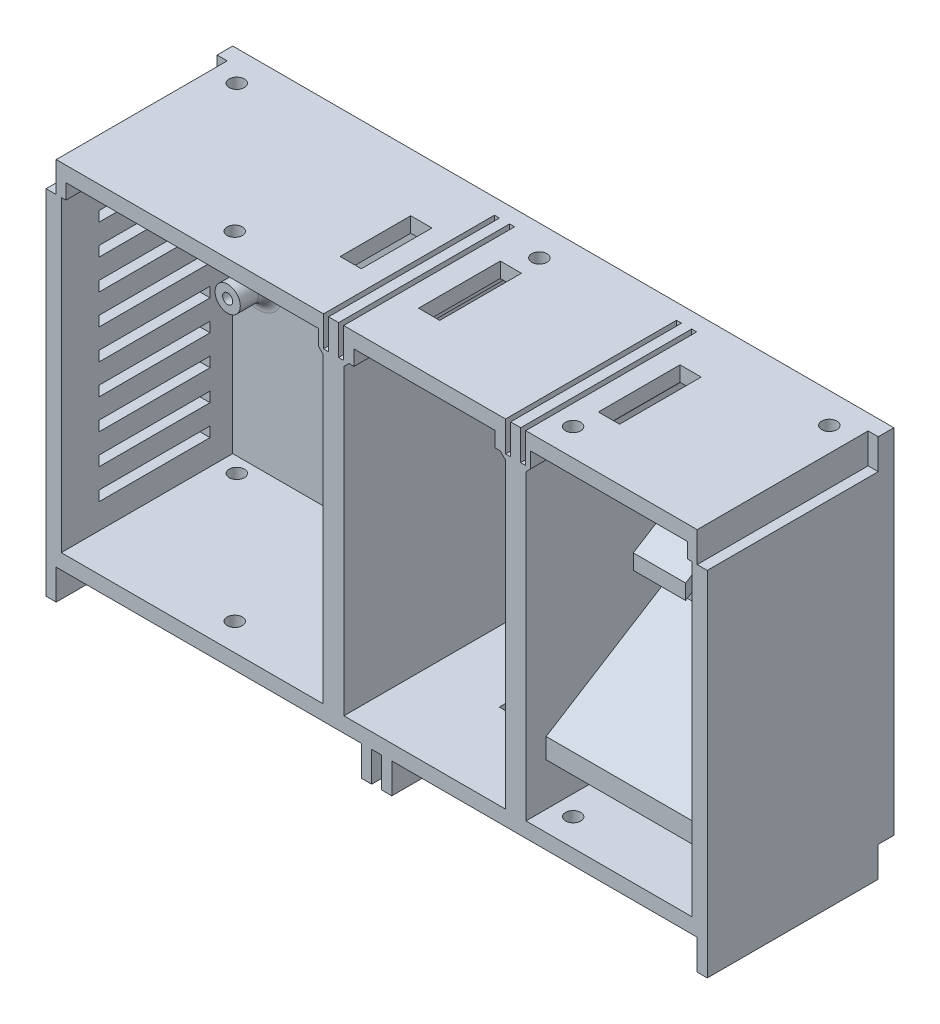
SolidWorks part; units mm, degrees
material "ABS"
ref_plane "Alzado" through (0, 0, 0) normal (0, 0, 1) x (1, 0, 0)
ref_plane "Planta" through (0, 0, 0) normal (0, 1, 0) x (1, 0, 0)
ref_plane "Vista lateral" through (0, 0, 0) normal (1, 0, 0) x (0, 0, -1)
sketch "Croquis1" plane through (0, 0, 0) normal (0, 0, 1) x (1, 0, 0)
  line L0 (0, 0) -> (2, 0)
  line L1 (2, 0) -> (2, 6)
  line L2 (55, 0) -> (55, 6)
  line L3 (55, 6) -> (2, 6)
  line L4 (56, 0) -> (56, 6)
  line L5 (56, 6) -> (58, 6)
  line L6 (58, 6) -> (58, 0)
  line L7 (58, 0) -> (59, 0)
  line L8 (59, 0) -> (59, 6)
  line L9 (91.1, 0) -> (91.1, 6)
  line L10 (59, 6) -> (91.1, 6)
  line L11 (92.1, 0) -> (92.1, 6)
  line L12 (92.1, 6) -> (94.1, 6)
  line L13 (94.1, 6) -> (94.1, 0)
  line L14 (95.1, 0) -> (95.1, 6)
  line L15 (129.1, 0) -> (129.1, 6)
  line L16 (129.1, 6) -> (95.1, 6)
  line L17 (0, 0) -> (0, -64)
  line L18 (0, -64) -> (131.1, -64)
  line L19 (131.1, -64) -> (131.1, 0)
  line L20 (55, 0) -> (56, 0)
  line L21 (58, 0) -> (59, 0)
  line L22 (129.1, 0) -> (131.1, 0)
  line L23 (94.1, 0) -> (95.1, 0)
  line L24 (91.1, 0) -> (92.1, 0)
  line L25 (2, 0) -> (129.1, 0)
  point P3 (2, 0)
  point P4 (129.1, 0)
  point P5 (55, 0)
  point P10 (56, 0)
  point P11 (58, 0)
  point P12 (59, 0)
  point P15 (91.1, 0)
  point P22 (92.1, 0)
  point P23 (94.1, 0)
  point P24 (95.1, 0)
  dimension "D1" = 131.1
  dimension "D2" = 2
  dimension "D3" = 2
  dimension "D4" = 55
  dimension "D5" = 6
  dimension "D6" = 1
  dimension "D7" = 2
  dimension "D8" = 1
  dimension "D9" = 32.1
  dimension "D10" = 1
  dimension "D11" = 2
  dimension "D12" = 1
  dimension "D13" = 64
extrude "Saliente-Extruir1" add sketch "Croquis1" along normal blind 34 contours L8 L25 L9 L10 | L1 L25 L2 L3 | L14 L25 L15 L16 | L11 L25 L13 L12 | L4 L25 L6 L5 region at (28.5, 3, 0) region at (57, 3, 0) region at (112.1, 3, 0) region at (75.05, 3, 0) region at (93.1, 3, 0)
sketch "Croquis2" plane through (0, 0, 0) normal (0, 0, 1) x (1, 0, 0)
  line L1 (2, -64) -> (129.1, -64)
  line L3 (129.1, 0) -> (2, 0)
  line L5 (129.1, 0) -> (131.1, 0)
  line L7 (129.1, -64) -> (131.1, -64)
  line L8 (131.1, 0) -> (131.1, -64)
  line L9 (2, -64) -> (0, -64)
  line L11 (2, 0) -> (0, 0)
  line L12 (0, -64) -> (0, 0)
  dimension "D1" = 64
  dimension "D2" = 2
  dimension "D3" = 2
extrude "Saliente-Extruir2" add sketch "Croquis2" along normal blind 3
sketch "Croquis3" plane through (0, 0, 3) normal (0, 0, 1) x (1, 0, 0)
  line L0 (0, -64) -> (131.1, -64) construction
  line L1 (131.1, 0) -> (128.1, 0)
  line L2 (131.1, 0) -> (131.1, -64)
  line L3 (131.1, -64) -> (128.1, -64)
  line L4 (128.1, 0) -> (128.1, -61)
  line L6 (0, 0) -> (3, 0)
  line L7 (0, 0) -> (0, -64)
  line L8 (0, -64) -> (3, -64)
  line L9 (3, 0) -> (3, -61)
  line L10 (3, -64) -> (128.1, -64)
  line L12 (3, -61) -> (128.1, -61)
  dimension "D1" = 3
  dimension "D2" = 3
  dimension "D3" = 3
extrude "Saliente-Extruir3" add sketch "Croquis3" along normal up to vertex (31 mm away) up to point (129.1, 0, 34)
sketch "Croquis4" plane through (0, 0, 0) normal (0, 0, -1) x (-1, 0, 0)
  line L24 (-59, 0) -> (-59, 6)
  line L25 (-59, 6) -> (-91.1, 6)
  line L26 (-91.1, 6) -> (-91.1, 0)
  line L27 (-91.1, 0) -> (-92.1, 0)
  line L28 (-92.1, 0) -> (-92.1, 6)
  line L29 (-92.1, 6) -> (-94.1, 6)
  line L30 (-94.1, 6) -> (-94.1, 0)
  line L31 (-94.1, 0) -> (-95.1, 0)
  line L32 (-95.1, 0) -> (-95.1, 6)
  line L33 (-95.1, 6) -> (-129.1, 6)
  line L34 (-129.1, 6) -> (-129.1, 0)
  line L35 (-129.1, 0) -> (-131.1, 0)
  line L36 (-131.1, 0) -> (-131.1, -64)
  line L37 (-131.1, -64) -> (0, -64)
  line L38 (0, -64) -> (0, 0)
  line L39 (0, 0) -> (-2, 0)
  line L40 (-2, 0) -> (-2, 6)
  line L41 (-2, 6) -> (-55, 6)
  line L42 (-55, 6) -> (-55, 0)
  line L43 (-55, 0) -> (-56, 0)
  line L44 (-56, 0) -> (-56, 6)
  line L45 (-56, 6) -> (-58, 6)
  line L46 (-58, 6) -> (-58, 0)
  line L47 (-58, 0) -> (-59, 0)
  line L48 (-59, 0) -> (-59, 6)
  line L49 (-59, 6) -> (-91.1, 6)
  line L50 (-91.1, 6) -> (-91.1, 0)
  line L51 (-91.1, 0) -> (-92.1, 0)
  line L52 (-92.1, 0) -> (-92.1, 6)
  line L53 (-92.1, 6) -> (-94.1, 6)
  line L54 (-94.1, 6) -> (-94.1, 0)
  line L55 (-94.1, 0) -> (-95.1, 0)
  line L56 (-95.1, 0) -> (-95.1, 6)
  line L57 (-95.1, 6) -> (-129.1, 6)
  line L58 (-129.1, 6) -> (-129.1, 0)
  line L59 (-129.1, 0) -> (-131.1, 0)
  line L60 (-131.1, 0) -> (-131.1, -64)
  line L61 (-131.1, -64) -> (0, -64)
  line L62 (0, -64) -> (0, 0)
  line L63 (0, 0) -> (-2, 0)
  line L64 (-2, 0) -> (-2, 6)
  line L65 (-2, 6) -> (-55, 6)
  line L66 (-55, 6) -> (-55, 0)
  line L67 (-55, 0) -> (-56, 0)
  line L68 (-56, 0) -> (-56, 6)
  line L69 (-56, 6) -> (-58, 6)
  line L70 (-58, 6) -> (-58, 0)
  line L71 (-58, 0) -> (-59, 0)
  dimension "D1" = 0
extrude "Saliente-Extruir4" add sketch "Croquis4" along normal blind 3
sketch "Croquis5" plane through (0, 0, 3) normal (0, 0, 1) x (1, 0, 0)
  line L1 (128.1, -61) -> (3, -61) construction
  line L23 (54.95, 0.05) -> (59.05, 0.05)
  line L24 (55, 0) -> (55, 6) construction
  line L25 (59, 0) -> (59, 6) construction
  line L26 (58, 0) -> (56, 0) construction
  line L27 (54.95, 0.05) -> (54.95, -61)
  line L28 (59.05, 0.05) -> (59.05, -61)
  line L29 (91.05, 0.05) -> (95.15, 0.05)
  line L30 (91.1, 0) -> (91.1, 6) construction
  line L31 (95.1, 0) -> (95.1, 6) construction
  line L32 (95.1, 0) -> (94.1, 0) construction
  line L33 (91.05, 0.05) -> (91.05, -61)
  line L34 (128.1, -61) -> (3, -61) construction
  line L35 (91.05, -61) -> (95.15, -61)
  line L36 (95.15, -61) -> (95.15, 0.05)
  line M6 (128.1, 0) -> (95.1, 0)
  line M7 (95.1, 0) -> (94.1, 0)
  line M8 (94.1, 0) -> (92.1, 0)
  line M9 (92.1, 0) -> (91.1, 0)
  line M10 (91.1, 0) -> (59, 0)
  line M11 (59, 0) -> (58, 0)
  line M12 (58, 0) -> (56, 0)
  line M13 (56, 0) -> (55, 0)
  line M14 (55, 0) -> (3, 0)
  line M16 (3, -61) -> (128.1, -61)
  dimension "D1" = 0.05
  dimension "D2" = 0.05
  dimension "D3" = 0.05
  dimension "D4" = 0.05
  dimension "D5" = 0.05
  dimension "D6" = 0.05
extrude "Saliente-Extruir10" add sketch "Croquis5" along normal up to vertex (31 mm away) contours L28 L27 M10 M11 M12 M13 M14 M16 | L36 L33 M16 M6 M7 M8 M9 M10 region at (57, -30.5, 3) region at (93.1, -30.5, 3) up to point (59, 0, 34)
sketch "Croquis6" plane through (0, 0, 0) normal (0, -1, 0) x (1, 0, 0)
  line L0 (0, 34) -> (0, -3) construction
  line L1 (0, 15.5) -> (131.1, 15.5) construction
  line L2 (131.1, 34) -> (131.1, -3) construction
  line L3 (51, 8.5) -> (51, 22.5)
  line L4 (51, 22.5) -> (46.8, 22.5)
  line L5 (46.8, 22.5) -> (46.8, 8.5)
  line L6 (46.8, 8.5) -> (51, 8.5)
  line L7 (99.1, 7.4) -> (99.1, 23.6)
  line L8 (99.1, 23.6) -> (103.3, 23.6)
  line L9 (103.3, 23.6) -> (103.3, 7.4)
  line L10 (103.3, 7.4) -> (99.1, 7.4)
  line L11 (63.45, 7.4) -> (63.45, 23.6)
  line L12 (63.45, 23.6) -> (67.65, 23.6)
  line L13 (67.65, 23.6) -> (67.65, 7.4)
  line L14 (67.65, 7.4) -> (63.45, 7.4)
  point P6 (99.1, 15.5)
  point P9 (51, 15.5)
  point P15 (99.1, 15.5)
  point P17 (63.45, 15.5)
  point P21 (63.45, 15.5)
  dimension "D1" = 51
  dimension "D2" = 4.2
  dimension "D3" = 14
  dimension "D4" = 32
  dimension "D5" = 16.2
  dimension "D6" = 4.2
  dimension "D7" = 12.45
extrude "Cortar-Extruir1" cut sketch "Croquis6" against normal up to next
sketch "Croquis7" plane through (0, 0, 34) normal (0, 0, 1) x (1, 0, 0)
  line L0 (3, 0) -> (54.95, 0) construction
  line L1 (28.975, 0) -> (28.975, 3)
  line L2 (3.925, 3) -> (54.025, 3)
  line L3 (54.025, 3) -> (54.025, 0)
  line L4 (3.925, 0) -> (54.025, 0)
  line L5 (3.925, 3) -> (3.925, 0)
  line L6 (75.05, 0) -> (75.05, 3)
  line L7 (59.05, 0) -> (91.05, 0) construction
  line L8 (75.05, 3) -> (89.05, 3)
  line L9 (89.05, 3) -> (89.05, 0)
  line L10 (89.05, 0) -> (75.05, 0)
  line L11 (75.05, 3) -> (61.05, 3)
  line L12 (61.05, 3) -> (61.05, 0)
  line L13 (61.05, 0) -> (75.05, 0)
  line L14 (61.05, 3) -> (75.05, 3)
  line L15 (111.625, 0) -> (111.625, 3)
  line L16 (95.15, 0) -> (128.1, 0) construction
  line L17 (111.625, 3) -> (127.225, 3)
  line L18 (127.225, 3) -> (127.225, 0)
  line L19 (127.225, 0) -> (111.625, 0)
  line L20 (111.625, 0) -> (96.025, 0)
  line L21 (96.025, 0) -> (96.025, 3)
  line L22 (96.025, 3) -> (111.625, 3)
  line M5 (59.05, 0) -> (91.05, 0)
  line M10 (95.15, 0) -> (128.1, 0)
  line M37 (3, 0) -> (54.95, 0)
  dimension "D1" = 25.05
  dimension "D2" = 3
  dimension "D3" = 14
  dimension "D4" = 15.6
extrude "Cortar-Extruir2" cut sketch "Croquis7" against normal up to vertex (31 mm away) contours L3 L2 L1 M37 | L2 L5 L1 M37 | L11 L12 L6 M5 | L9 L8 L6 M5 | L22 L21 L15 M10 | L18 L17 L15 M10 region at (16.45, 1.5, 34) region at (41.5, 1.5, 34) region at (68.05, 1.5, 34) region at (82.05, 1.5, 34) region at (103.825, 1.5, 34) region at (119.425, 1.5, 34) up to point (54.95, 0, 3)
sketch "Croquis22" plane through (0, 0, 3) normal (0, 0, 1) x (1, 0, 0)
  line L0 (95.15, 0) -> (95.15, -61) construction
  line L1 (95.15, -61) -> (128.1, -61) construction
  line L2 (128.1, -61) -> (128.1, 0) construction
  line L3 (128.1, 0) -> (127.225, 0) construction
  line L4 (127.225, 0) -> (127.225, 3) construction
  line L5 (127.225, 3) -> (96.025, 3) construction
  line L6 (96.025, 3) -> (96.025, 0) construction
  line L7 (96.025, 0) -> (95.15, 0) construction
  line L8 (91.05, -61) -> (91.05, 0) construction
  line L9 (91.05, 0) -> (89.05, 0) construction
  line L10 (89.05, 0) -> (89.05, 3) construction
  line L11 (89.05, 3) -> (61.05, 3) construction
  line L12 (61.05, 3) -> (61.05, 0) construction
  line L13 (61.05, 0) -> (59.05, 0) construction
  line L14 (59.05, 0) -> (59.05, -61) construction
  line L15 (59.05, -61) -> (91.05, -61) construction
  line L16 (54.95, -61) -> (54.95, 0) construction
  line L17 (54.95, 0) -> (54.025, 0) construction
  line L18 (54.025, 0) -> (54.025, 3) construction
  line L19 (54.025, 3) -> (3.925, 3) construction
  line L20 (3.925, 3) -> (3.925, 0) construction
  line L21 (3.925, 0) -> (3, 0) construction
  line L22 (3, 0) -> (3, -61) construction
  line L23 (3, -61) -> (54.95, -61) construction
  line L24 (95.15, 0) -> (95.15, -61)
  line L25 (95.15, -61) -> (128.1, -61)
  line L26 (128.1, -61) -> (128.1, 0)
  line L27 (128.1, 0) -> (127.225, 0)
  line L28 (127.225, 0) -> (127.225, 3)
  line L29 (127.225, 3) -> (96.025, 3)
  line L30 (96.025, 3) -> (96.025, 0)
  line L31 (96.025, 0) -> (95.15, 0)
  line L32 (91.05, -61) -> (91.05, 0)
  line L33 (91.05, 0) -> (89.05, 0)
  line L34 (89.05, 0) -> (89.05, 3)
  line L35 (89.05, 3) -> (61.05, 3)
  line L36 (61.05, 3) -> (61.05, 0)
  line L37 (61.05, 0) -> (59.05, 0)
  line L38 (59.05, 0) -> (59.05, -61)
  line L39 (59.05, -61) -> (91.05, -61)
  line L40 (54.95, -61) -> (54.95, 0)
  line L41 (54.95, 0) -> (54.025, 0)
  line L42 (54.025, 0) -> (54.025, 3)
  line L43 (54.025, 3) -> (3.925, 3)
  line L44 (3.925, 3) -> (3.925, 0)
  line L45 (3.925, 0) -> (3, 0)
  line L46 (3, 0) -> (3, -61)
  line L47 (3, -61) -> (54.95, -61)
extrude "Cortar-Extruir8" cut sketch "Croquis22" against normal blind 3 contours L40 L41 L42 L43 L44 L45 L46 L47 | L32 L33 L34 L35 L36 L37 L38 L39 | L24 L25 L26 L27 L28 L29 L30 L31
sketch "Croquis24" plane through (2, 0, 0) normal (-1, 0, 0) x (0, 0, 1)
  line L0 (34, 0) -> (-3, 0) construction
  line L5 (0.1, 0) -> (-4.3164, 0)
  line L6 (0.1, 0) -> (0.1, 6.5451)
  line L7 (0.1, 6.5451) -> (-4.3164, 6.5451)
  line L8 (-4.3164, 0) -> (-4.3164, 6.5451)
  line L9 (0, 0) -> (0, 8.0802) construction
  dimension "D1" = 0.1
extrude "Cortar-Extruir11" cut sketch "Croquis24" against normal through all contours L6 L5 L8 L7
sketch "Croquis25" plane through (0, 0, 0.1) normal (0, 0, -1) x (-1, 0, 0)
  line L1 (-2, 0) -> (-55, 0)
  line L2 (-2, 0) -> (-2, 6)
  line L3 (-2, 6) -> (-55, 6)
  line L4 (-55, 0) -> (-55, 6)
  line L5 (-59, 6) -> (-91.1, 6)
  line L6 (-59, 6) -> (-59, 0)
  line L7 (-59, 0) -> (-91.1, 0)
  line L8 (-91.1, 6) -> (-91.1, 0)
  line L9 (-95.1, 6) -> (-129.1, 6)
  line L10 (-95.1, 6) -> (-95.1, 0)
  line L11 (-95.1, 0) -> (-129.1, 0)
  line L12 (-129.1, 6) -> (-129.1, 0)
extrude "Saliente-Extruir15" add sketch "Croquis25" against normal blind 1
sketch "Croquis26" plane through (0, 0, 0) normal (0, 0, 1) x (1, 0, 0)
  line L0 (4, -60) -> (54.1, -60)
  line L1 (4, -60) -> (4, -4.1)
  line L2 (4, -4.1) -> (54.1, -4.1)
  line L3 (54.1, -60) -> (54.1, -4.1)
  line L4 (4, -60) -> (54.1, -4.1) construction
  line L5 (4, -4.1) -> (54.1, -60) construction
  line L6 (36.1, -45) -> (46.1, -45)
  line L7 (36.1, -45) -> (36.1, -39)
  line L8 (36.1, -39) -> (46.1, -39)
  line L9 (46.1, -45) -> (46.1, -39)
  line L10 (3, -61) -> (54.95, -61) construction
  line L11 (3, 0) -> (3, -61) construction
  line L12 (54.95, -61) -> (54.95, 0) construction
  circle A0 centre (24, -8.1) radius 1
  circle A1 centre (8, -28.9) radius 1
  circle A2 centre (24, -8.1) radius 2.5
  circle A3 centre (8, -28.9) radius 2.5
  point P0 (29.05, -32.05)
  point P5 (24, -8.1)
  point P8 (8, -28.9)
  dimension "D6" = 2
  dimension "D7" = 5
  dimension "D1" = 1
  dimension "D2" = 55.9
  dimension "D3" = 1
  dimension "D4" = 4
  dimension "D5" = 24.8
  dimension "D8" = 4
  dimension "D9" = 20
  dimension "D10" = 8
  dimension "D11" = 15
  dimension "D12" = 6
  dimension "D13" = 10
  dimension "D14" = 0.85
extrude "Saliente-Extruir16" add sketch "Croquis26" along normal blind 6 contours L6 L9 L8 L7 | A2 A0 | A3 A1 region at (41.1, -42, 0) region at (21.5707, -8.1, 0) region at (5.5707, -28.9, 0)
fillet "Redondeo1" radius 2.4 3 edges at (10.5, -28.9, 0) (26.5, -8.1, 0) (46.1, -42, 0)
chamfer "Chaflán1" distance 1 angle 45 4 edges at (54.95, 0, 17.05) (95.15, 0, 17.05) (91.05, 0, 17.05) (59.05, 0, 17.05)
sketch "Croquis10" plane through (0, 0, 0) normal (-1, 0, 0) x (0, 0, 1)
  line L0 (15.5, -64) -> (15.5, 6) construction
  line L1 (34, -64) -> (-3, -64) construction
  line L3 (4.5, -50) -> (4.5, -48)
  line L4 (4.5, -56) -> (26.5, -56)
  line L5 (4.5, -56) -> (4.5, -54)
  line L6 (4.5, -54) -> (26.5, -54)
  line L7 (26.5, -56) -> (26.5, -54)
  line L8 (4.5, -56) -> (26.5, -54) construction
  line L9 (4.5, -54) -> (26.5, -56) construction
  line L10 (4.5, -50) -> (26.5, -50)
  line L11 (26.5, -50) -> (26.5, -48)
  line L12 (4.5, -48) -> (26.5, -48)
  line L13 (4.5, -44) -> (4.5, -42)
  line L14 (4.5, -44) -> (26.5, -44)
  line L15 (26.5, -44) -> (26.5, -42)
  line L16 (4.5, -42) -> (26.5, -42)
  line L17 (4.5, -38) -> (4.5, -36)
  line L18 (4.5, -38) -> (26.5, -38)
  line L19 (26.5, -38) -> (26.5, -36)
  line L20 (4.5, -36) -> (26.5, -36)
  line L21 (4.5, -32) -> (4.5, -30)
  line L22 (4.5, -32) -> (26.5, -32)
  line L23 (26.5, -32) -> (26.5, -30)
  line L24 (4.5, -30) -> (26.5, -30)
  line L25 (4.5, -26) -> (4.5, -24)
  line L26 (4.5, -26) -> (26.5, -26)
  line L27 (26.5, -26) -> (26.5, -24)
  line L28 (4.5, -24) -> (26.5, -24)
  line L29 (4.5, -20) -> (4.5, -18)
  line L30 (4.5, -20) -> (26.5, -20)
  line L31 (26.5, -20) -> (26.5, -18)
  line L32 (4.5, -18) -> (26.5, -18)
  line L33 (4.5, -14) -> (4.5, -12)
  line L34 (4.5, -14) -> (26.5, -14)
  line L35 (26.5, -14) -> (26.5, -12)
  line L36 (4.5, -12) -> (26.5, -12)
  line L37 (4.5, -8) -> (4.5, -6)
  line L38 (4.5, -8) -> (26.5, -8)
  line L39 (26.5, -8) -> (26.5, -6)
  line L40 (4.5, -6) -> (26.5, -6)
  point P6 (15.5, -55)
  dimension "D1" = 22
  dimension "D2" = 2
  dimension "D3" = 8
  dimension "D4" = 9
extrude "Cortar-Extruir3" cut sketch "Croquis10" against normal up to vertex (3 mm away) contours L4 L7 L6 L5 | L12 L3 L10 L11 | L16 L13 L14 L15 | L20 L17 L18 L19 | L24 L21 L22 L23 | L28 L25 L26 L27 | L32 L29 L30 L31 | L36 L33 L34 L35 | L40 L37 L38 L39 region at (0, -49, 15.5) region at (0, -55, 15.5) region at (0, -43, 15.5) region at (0, -37, 15.5) region at (0, -31, 15.5) region at (0, -25, 15.5) region at (0, -19, 15.5) region at (0, -13, 15.5) region at (0, -7, 15.5) up to point (3, -61, 34)
sketch "Croquis12" plane through (95.15, 0, 0) normal (1, 0, 0) x (0, 0, -1)
  line L0 (0, -29.7544) -> (-34, -51)
  line L1 (0, 0) -> (0, -61) construction
  line L2 (-34, -61) -> (-34, -1) construction
  line L4 (-34, -51) -> (-34, -55)
  line L5 (-34, -55) -> (0, -33.7544)
  line L6 (0, -29.7544) -> (0, -33.7544)
  dimension "D1" = 4
  dimension "D2" = 58
  dimension "D3" = 6
extrude "Saliente-Extruir12" add sketch "Croquis12" along normal up to surface (32.95 mm away) up to face at (128.1, -24.4, 13.62)
sketch "Croquis13" plane through (95.15, 0, 0) normal (1, 0, 0) x (0, 0, -1)
  line L0 (0, -29.7544) -> (0, -20.6544) construction
  line L2 (0, -20.6544) -> (-12.7207, -28.6032)
  line L4 (0, -29.7544) -> (-34, -51) construction
  line L6 (-12.7207, -25.6032) -> (0, -17.6544)
  line L7 (0, -17.6544) -> (0, -20.6544)
  line L8 (-12.7207, -28.6032) -> (-12.7207, -25.6032)
  line L9 (-34, -51) -> (-8.7351, -35.2127) construction
  line L10 (0, -29.7544) -> (-34, -51) construction
  line L11 (-6.7844, -33.9938) -> (-6.7844, -24.8938)
  line L12 (-6.7844, -33.9938) -> (0, -29.7544)
  line L13 (0, 0) -> (0, -29.7544) construction
  line M8 (-34, -51) -> (0, -29.7544)
  line M18 (0, -29.7544) -> (0, 0)
  dimension "D1" = 9.1
  dimension "D2" = 3
  dimension "D3" = 15
  dimension "D4" = 8
extrude "Saliente-Extruir17" add sketch "Croquis13" along normal up to surface (32.95 mm away) contours L11 L2 M8 M18 | L8 L2 L6 M18 region at (95.15, -27.3241, 3.3922) region at (95.15, -23.1288, 6.3604) up to face at (128.1, -16.1509, 13.62)
ref_plane "Plano1" through (0, -17.6544, 0) normal (0, -1, 0) x (-1, 0, 0)
sketch "Croquis38" plane through (0, -17.6544, 0) normal (0, -1, 0) x (-1, 0, 0)
  line L0 (-111.625, 0) -> (-111.625, -34.0311) construction
  line L1 (-128.1, 0) -> (-95.15, 0) construction
  line L2 (-111.625, 0) -> (-117.725, 0)
  line L3 (-117.725, 0) -> (-117.725, -26)
  line L4 (-117.725, -26) -> (-105.525, -26)
  line L5 (-111.625, 0) -> (-105.525, 0)
  line L6 (-105.525, 0) -> (-105.525, -26)
  dimension "D1" = 6.1
  dimension "D2" = 6.1
  dimension "D3" = 26
  dimension "D4" = 26
extrude "Cortar-Extruir12" cut sketch "Croquis38" along normal up to vertex (16.3394 mm away) contours L0 L2 L3 L4 | L5 L0 L4 L6 region at (108.575, -17.6544, 13) region at (114.675, -17.6544, 13) up to point (128.1, -33.9938, 6.7844)
sketch "Croquis40" plane through (0, 3, 0) normal (0, -1, 0) x (1, 0, 0)
  line L0 (0, 34) -> (0, -3) construction
  line L1 (3.925, 34) -> (54.025, 34) construction
  line L2 (131.1, 34) -> (131.1, -3) construction
  line L3 (0, -3) -> (131.1, -3) construction
  circle A0 centre (32, 28.6) radius 1.5
  circle A1 centre (99.1, 28.6) radius 1.5
  circle A2 centre (6.8, 3) radius 1.5
  circle A3 centre (124.3, 3) radius 1.5
  circle A4 centre (66.8, 3) radius 1.5
  dimension "D3" = 3
  dimension "D1" = 32
  dimension "D2" = 5.4
  dimension "D4" = 32
  dimension "D5" = 6.8
  dimension "D6" = 6
  dimension "D7" = 6.8
  dimension "D8" = 60
extrude "Cortar-Extruir13" cut sketch "Croquis40" against normal up to next
sketch "Croquis42" plane through (0, 0, 0) normal (0, -1, 0) x (1, 0, 0)
  line L0 (90.05, 0.1) -> (90.05, 34) construction
  line L1 (96.15, 0.1) -> (127.225, 0.1)
  line L2 (96.15, 0.1) -> (96.15, 1.1)
  line L3 (96.15, 1.1) -> (127.225, 1.1)
  line L4 (127.225, 0.1) -> (127.225, 1.1)
  line L5 (60.05, 0.1) -> (90.05, 0.1)
  line L6 (60.05, 0.1) -> (60.05, 1.1)
  line L7 (60.05, 1.1) -> (90.05, 1.1)
  line L8 (90.05, 0.1) -> (90.05, 1.1)
  line L9 (3, 34) -> (3, 0.1) construction
  line L10 (3, 1.1) -> (53.8965, 1.1)
  line L11 (3, 1.1) -> (3, 0)
  line L12 (3, 0) -> (53.8965, 0)
  line L13 (53.8965, 1.1) -> (53.8965, 0)
  line L14 (54.95, 0) -> (3, 0) construction
extrude "Saliente-Extruir18" add sketch "Croquis42" along normal blind 0.2
sketch "Croquis44" plane through (0, 0, 0) normal (0, 0, 1) x (1, 0, 0)
  line L0 (90.05, -0.2) -> (60.05, -0.2) construction
  line L1 (62.35, -22.2) -> (87.75, -22.2)
  line L2 (62.35, -22.2) -> (62.35, -56)
  line L3 (62.35, -56) -> (87.75, -56)
  line L4 (87.75, -22.2) -> (87.75, -56)
  line L5 (59.05, -1) -> (59.05, -61) construction
  line L6 (59.05, -61) -> (91.05, -61) construction
  line L7 (75.05, -56) -> (75.05, -22.2) construction
  line L8 (62.35, -39.1) -> (87.75, -39.1) construction
  circle A0 centre (65.65, -53.7) radius 2.5
  circle A1 centre (65.65, -53.7) radius 1.2
  circle A2 centre (84.25, -53.7) radius 2.5
  circle A3 centre (84.25, -53.7) radius 1.2
  circle A4 centre (84.75, -24.2) radius 2.5
  circle A5 centre (84.75, -24.2) radius 1.2
  circle A6 centre (65.35, -24.2) radius 2.5
  circle A7 centre (65.35, -24.2) radius 1.2
  point P6 (75.05, -0.2)
  point P7 (75.05, -22.2)
  point P8 (75.05, -56)
  dimension "D4" = 5
  dimension "D5" = 2.4
  dimension "D1" = 25.4
  dimension "D2" = 33.8
  dimension "D3" = 5
  dimension "D6" = 3.3
  dimension "D7" = 2.3
  dimension "D8" = 2.3
  dimension "D9" = 3.5
  dimension "D10" = 3
  dimension "D11" = 2
  dimension "D12" = 3
  dimension "D13" = 2
extrude "Saliente-Extruir19" add sketch "Croquis44" along normal blind 3 contours L3 A2 | L3 A2 A3 | L3 A0 | L3 A0 A1 | L1 A6 A7 | L1 A6 | L1 A4 A5 | L1 A4 region at (65.35, -21.9982, 0) region at (65.35, -22.2673, 0) region at (64.3097, -51.6722, 0) region at (65.65, -56.0803, 0) region at (84.75, -21.9982, 0) region at (84.75, -22.2673, 0) region at (82.9097, -51.6722, 0) region at (84.25, -56.0803, 0)
fillet "Redondeo2" radius 3 4 edges at (86.75, -53.7, 0) (68.15, -53.7, 0) (87.25, -24.2, 0) (67.85, -24.2, 0)
sketch "Croquis48" plane through (0, 0, 0) normal (-1, 0, 0) x (0, 0, 1)
  line L1 (-3, 0) -> (0.1, 0)
  line L2 (-3, 0) -> (-3, 6)
  line L3 (-3, 6) -> (0.1, 6)
  line L4 (0.1, 0) -> (0.1, 6)
extrude "Saliente-Extruir20" add sketch "Croquis48" against normal up to vertex (131.1 mm away) up to point (131.1, 0, -3)
sketch "Croquis49" plane through (0, 0, 34) normal (0, 0, 1) x (1, 0, 0)
  line L0 (2, 0) -> (2, -64) construction
  line L1 (0, -64) -> (131.1, -64) construction
  line L2 (129.1, 0) -> (129.1, -64) construction
  line L3 (66.55, -70) -> (66.55, -64)
  line L4 (2, -64) -> (0, -64)
  line L5 (0, -64) -> (0, -70)
  line L6 (0, -70) -> (2, -70)
  line L7 (2, -70) -> (2, -64)
  line L8 (129.1, -64) -> (131.1, -64)
  line L9 (131.1, -64) -> (131.1, -70)
  line L10 (131.1, -70) -> (129.1, -70)
  line L11 (129.1, -70) -> (129.1, -64)
  line L12 (65.55, -64) -> (68.55, -64)
  line L13 (68.55, -64) -> (68.55, -70)
  line L14 (68.55, -70) -> (66.55, -70)
  line L15 (62.55, -70) -> (62.55, -64)
  line L16 (62.55, -64) -> (65.55, -64)
  line L17 (64.55, -70) -> (64.55, -64)
  line L18 (64.55, -70) -> (62.55, -70)
  dimension "D1" = 6
  dimension "D2" = 3
  dimension "D3" = 2
  dimension "D4" = 2
extrude "Saliente-Extruir21" add sketch "Croquis49" against normal up to vertex (33.9 mm away) contours L6 L7 L4 L5 | L18 L17 L16 L15 | L14 L13 L12 L3 | L11 L10 L9 L8 region at (63.55, -67, 34) region at (67.55, -67, 34) region at (1, -67, 34) region at (130.1, -67, 34) up to point (2, 0, 0.1)
sketch "Croquis50" plane through (0, -64, 0) normal (0, -1, 0) x (1, 0, 0)
  circle A0 centre (124.3, 3) radius 1.5 construction
  circle A1 centre (99.1, 28.6) radius 1.5 construction
  circle A3 centre (6.8, 3) radius 1.5 construction
  circle A4 centre (32, 28.6) radius 1.5 construction
  circle A5 centre (124.3, 3) radius 1.5
  circle A6 centre (99.1, 28.6) radius 1.5
  circle A8 centre (6.8, 3) radius 1.5
  circle A9 centre (32, 28.6) radius 1.5
extrude "Cortar-Extruir14" cut sketch "Croquis50" against normal up to surface (3 mm away) up to face at (28.975, -61, 17)
sketch "Croquis51" plane through (0, 0, 0) normal (-1, 0, 0) x (0, 0, 1)
  line L0 (0.1, -64) -> (-3, -64) construction
  line L1 (-3, 6) -> (-2.9, 6)
  line L2 (-3, 6) -> (-3, -64)
  line L3 (-3, -64) -> (-2.9, -64)
  line L4 (-2.9, 6) -> (-2.9, -64)
  dimension "D1" = 0.1
extrude "Cortar-Extruir15" cut sketch "Croquis51" against normal through all
sketch "Croquis52" plane through (0, -64, 0) normal (0, -1, 0) x (1, 0, 0)
  line L0 (68.55, 0.1) -> (68.55, 34) construction
  line L1 (72.95, 17.1) -> (78.95, 17.1)
  line L2 (72.95, 17.1) -> (72.95, 9.1)
  line L3 (72.95, 9.1) -> (78.95, 9.1)
  line L4 (78.95, 17.1) -> (78.95, 9.1)
  line L5 (131.1, -2.9) -> (0, -2.9) construction
  dimension "D1" = 4.4
  dimension "D2" = 12
  dimension "D3" = 8
  dimension "D4" = 6
extrude "Cortar-Extruir16" cut sketch "Croquis52" against normal up to vertex (3 mm away) up to point (59.05, -61, 34)
sketch "Croquis53" plane through (0, 0, 34) normal (0, 0, 1) x (1, 0, 0)
  line L0 (128.1, 0) -> (128.1, -51) construction
  line L1 (95.15, -51) -> (128.1, -51)
  line L2 (95.15, -51) -> (95.15, -55)
  line L3 (95.15, -55) -> (128.1, -55)
  line L4 (128.1, -51) -> (128.1, -55)
  line L5 (95.15, -51) -> (128.1, -51)
  line L6 (95.15, -51) -> (95.15, -48.3278)
  line L7 (95.15, -48.3278) -> (128.1, -48.3278)
  line L8 (128.1, -51) -> (128.1, -48.3278)
extrude "Cortar-Extruir17" cut sketch "Croquis53" against normal blind 4 contours L4 L1 L2 L3 | L1 L8 L7 L6 region at (111.625, -49.6639, 34) region at (111.625, -53, 34)
sketch "Croquis54" plane through (0, 0, -2.9) normal (0, 0, -1) x (-1, 0, 0)
  line L1 (-131.1, 6) -> (0, 6)
  line L2 (-131.1, 6) -> (-131.1, -64)
  line L3 (-131.1, -64) -> (0, -64)
  line L4 (0, 6) -> (0, -64)
extrude "Saliente-Extruir22" add sketch "Croquis54" along normal blind 0.1
